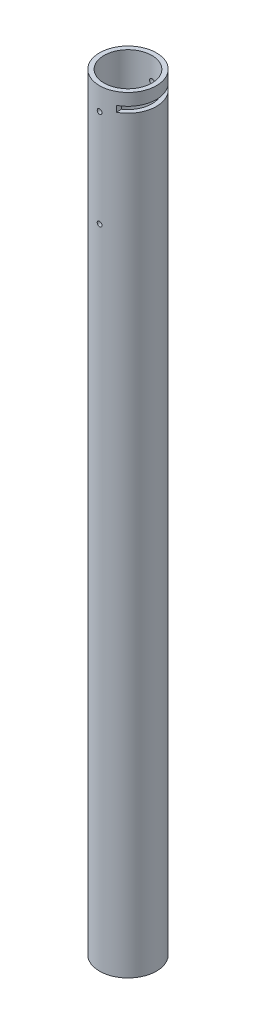
SolidWorks part; units mm, degrees
ref_plane "Front Plane" through (0, 0, 0) normal (0, 0, 1) x (1, 0, 0)
ref_plane "Top Plane" through (0, 0, 0) normal (0, 1, 0) x (1, 0, 0)
ref_plane "Right Plane" through (0, 0, 0) normal (1, 0, 0) x (0, 0, -1)
sketch "Sketch1" plane through (0, 0, 0) normal (0, 1, 0) x (1, 0, 0)
  circle A0 centre (0, 0) radius 30.1625
  circle A1 centre (0, 0) radius 25.4
  dimension "D1" = 60.325
  dimension "D2" = 50.8
extrude "Boss-Extrude1" add sketch "Sketch1" along normal blind 812.8
sketch "Sketch4" plane through (0, 0, 0) normal (0, 0, 1) x (1, 0, 0)
  line L0 (30.1625, 812.8) -> (30.1625, 800.1)
  line L1 (30.1625, 0) -> (30.1625, 812.8) construction
  line L3 (30.1625, 800.1) -> (14.2875, 800.1)
  line L6 (14.2875, 800.1) -> (14.2875, 793.75)
  line L8 (14.2875, 793.75) -> (30.1625, 793.75)
  line L9 (30.1625, 793.75) -> (30.1625, 800.1)
  line L10 (0, 812.8) -> (0, 788.9875) construction
  line L11 (25.4, 812.8) -> (-25.4, 812.8) construction
  line L12 (0, 788.9875) -> (0, 685.8) construction
  line L13 (30.1625, 812.8) -> (-30.1625, 812.8) construction
  line L14 (14.2875, 796.925) -> (30.1625, 796.925) construction
  circle A2 centre (0, 788.9875) radius 2.54
  circle A3 centre (0, 685.8) radius 2.54
  dimension "D4" = 5.08
  dimension "D1" = 6.35
  dimension "D2" = 15.875
  dimension "D3" = 15.875
  dimension "D5" = 23.8125
  dimension "D6" = 127
extrude "Cut-Extrude2" cut sketch "Sketch4" against normal through all both and the other way through all contours A3 | A2 | L8 L9 L3 L6 region at (22.225, 796.925, 0) region at (0, 788.9875, 0) region at (0, 685.8, 0)
